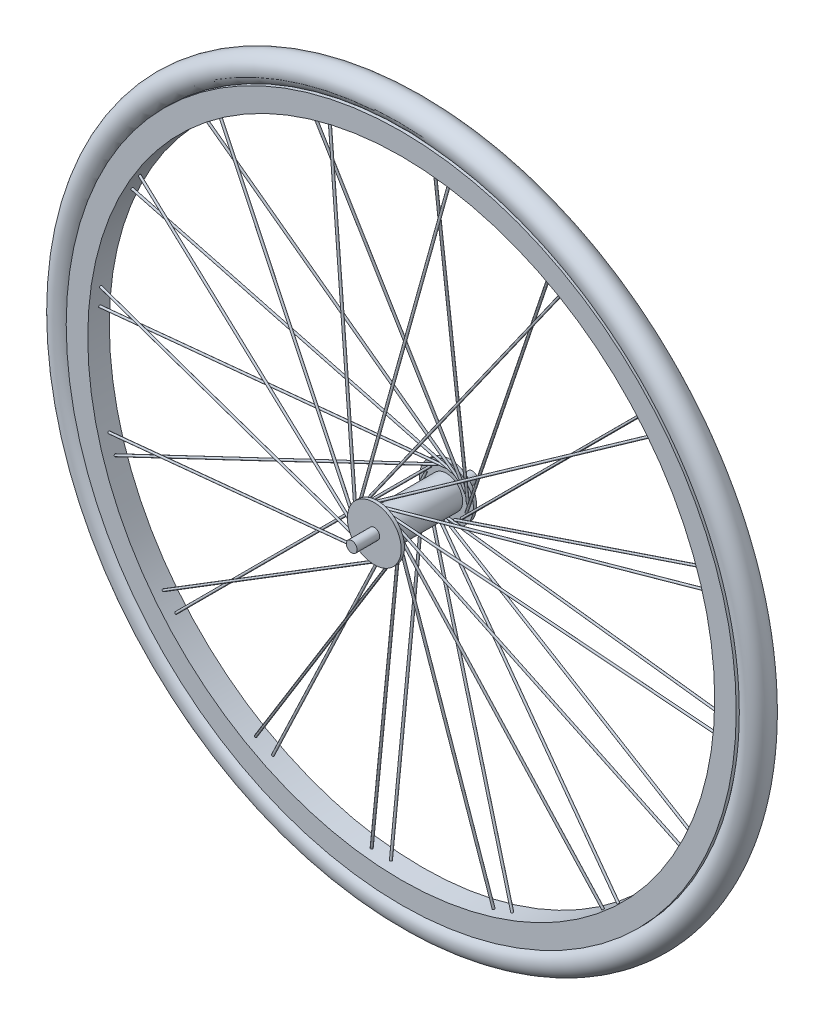
SolidWorks part; units mm, degrees
material "6061-T6 (SS)"
ref_plane "Alzado" through (0, 0, 0) normal (0, 0, 1) x (1, 0, 0)
ref_plane "Planta" through (0, 0, 0) normal (0, 1, 0) x (1, 0, 0)
ref_plane "Vista lateral" through (0, 0, 0) normal (1, 0, 0) x (0, 0, -1)
sketch "Sk_Eje" plane through (0, 0, 0) normal (0, 0, 1) x (1, 0, 0)
  circle A0 centre (0, 0) radius 5
  point P0 (0, 0)
  dimension "D1" = 10
extrude "Eje" add sketch "Sk_Eje" along normal blind 106 and the other way blind 6
sketch "Sk_Buje" plane through (0, 0, 0) normal (0, 0, 1) x (1, 0, 0)
  circle A0 centre (0, 0) radius 15
  point P0 (0, 0)
  dimension "D1" = 30
extrude "Buje" add sketch "Sk_Buje" along normal blind 70 from offset 15
sketch "Sk_Pestana_izq" plane through (0, 0, 0) normal (0, 0, 1) x (1, 0, 0)
  circle A0 centre (0, 0) radius 25
  point P0 (0, 0)
  dimension "D1" = 50
extrude "Pestana_izq" add sketch "Sk_Pestana_izq" along normal blind 3 from offset 15
sketch "Sk_Pestana_dcha" plane through (0, 0, 0) normal (0, 0, 1) x (1, 0, 0)
  circle A0 centre (0, 0) radius 25
  point P0 (0, 0)
  dimension "D1" = 50
extrude "Pestana_dcha" add sketch "Sk_Pestana_dcha" along normal blind 3 from offset 82
sketch "Sk_Llanta" plane through (0, 0, 0) normal (0, 0, 1) x (1, 0, 0)
  circle A0 centre (0, 0) radius 311
  circle A1 centre (0, 0) radius 291
  point P0 (0, 0)
  dimension "D1" = 622
  dimension "D2" = 582
extrude "Llanta" add sketch "Sk_Llanta" along normal blind 20 from offset 40
sketch "Sk_Cubierta" plane through (0, 0, 0) normal (0, 1, 0) x (1, 0, 0)
  line L0 (0, 950) -> (0, -1050) construction
  circle A0 centre (321.5, -50) radius 12.5
  point P0 (0, 0)
  dimension "D1" = 25
  dimension "D2" = 321.5
  dimension "D3" = 50
revolve "Cubierta" add sketch "Sk_Cubierta" angle 360 about L0
sketch3d "Eje_Radio_izq"
  line L0 (0, 20, 18) -> (-294.327, 20, 50)
  point P2 (-147.1635, 20, 34)
ref_plane "Plano_Radio_izq" through (-147.1635, 20, 34) normal (-0.9941, 0, 0.1081) x (0.1081, 0, 0.9941)
sketch "Sk_Radio_izq" plane through (-147.1635, 20, 34) normal (-0.9941, 0, 0.1081) x (0.1081, 0, 0.9941)
  circle A0 centre (0, 0) radius 1
extrude "Radio_izq" add sketch "Sk_Radio_izq" along normal mid plane 296.0615
sketch3d "Eje_Matriz_radios_izq"
  line L0 (0, 0, -500) -> (0, 0, 500)
pattern_circular "Matriz_radios_izq" count 16 over 360 about axis through (0, 0, -500) along (0, 0, 1) of "Radio_izq"
sketch3d "Eje_Radio_dcha"
  line L0 (3.902, 19.616, 82) -> (292.57, -37.805, 50)
  point P2 (148.236, -9.0945, 66)
ref_plane "Plano_Radio_dcha" through (148.236, -9.0945, 66) normal (0.975, -0.194, -0.1081) x (-0.106, 0.0211, -0.9941)
sketch "Sk_Radio_dcha" plane through (148.236, -9.0945, 66) normal (0.975, -0.194, -0.1081) x (-0.106, 0.0211, -0.9941)
  circle A0 centre (0, 0) radius 1
extrude "Radio_dcha" add sketch "Sk_Radio_dcha" along normal mid plane 296.0581
sketch3d "Eje_Matriz_radios_dcha"
  line L0 (0, 0, -500) -> (0, 0, 500)
pattern_circular "Matriz_radios_dcha" count 16 over 360 about axis through (0, 0, -500) along (0, 0, 1) of "Radio_dcha"
equation "\"diametro_cubierta\"= 668"
equation "\"longitud_eje\"= 100"
equation "\"ancho_buje\"= 70"
equation "\"diametro_llanta\"= 622"
